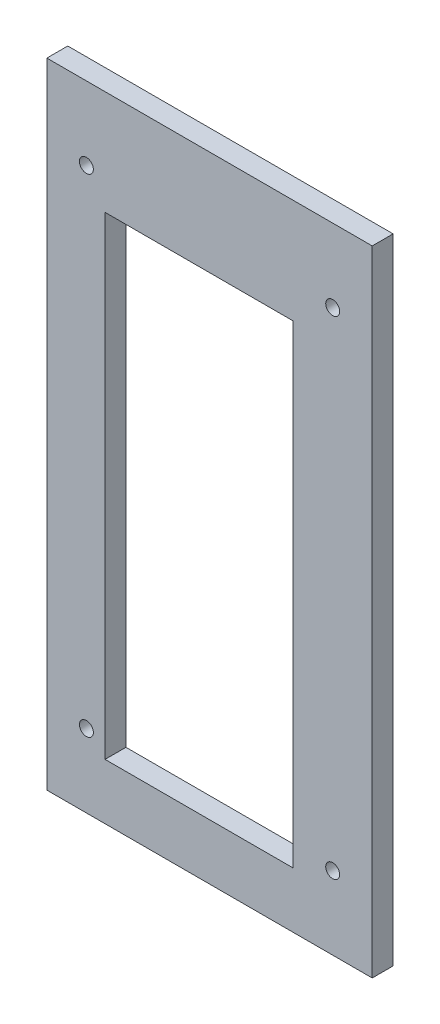
SolidWorks part; units mm, degrees
ref_plane "Front Plane" through (0, 0, 0) normal (0, 0, 1) x (1, 0, 0)
ref_plane "Top Plane" through (0, 0, 0) normal (0, 1, 0) x (1, 0, 0)
ref_plane "Right Plane" through (0, 0, 0) normal (1, 0, 0) x (0, 0, -1)
sketch "Sketch1" plane through (0, 0, 0) normal (0, 0, 1) x (1, 0, 0)
  line L0 (-17.675, 45.5) -> (-17.675, -45.5) construction
  line L1 (-23.35, 45.5) -> (23.35, 45.5)
  line L2 (-23.35, 45.5) -> (-23.35, -45.5)
  line L3 (-23.35, -45.5) -> (23.35, -45.5)
  line L4 (23.35, 45.5) -> (23.35, -45.5)
  line L5 (-23.35, 45.5) -> (23.35, -45.5) construction
  line L6 (-23.35, -45.5) -> (23.35, 45.5) construction
  line L7 (17.675, 45.5) -> (17.675, -45.5) construction
  line L8 (-15, 45.5) -> (-15, -45.5) construction
  line L9 (-15, 30.5) -> (12, 30.5)
  line L10 (-15, 30.5) -> (-15, -37.5)
  line L11 (-15, -37.5) -> (12, -37.5)
  line L12 (12, 30.5) -> (12, -37.5)
  line L13 (-20.35, -45.5) -> (-20.35, 45.5) construction
  line L14 (15, 45.5) -> (15, -45.5) construction
  line L15 (20.35, -45.5) -> (20.35, 45.5) construction
  line L16 (-21, 11.5) -> (21, 11.5) construction
  line L17 (-23.35, 0) -> (23.35, 0) construction
  line L18 (0, 45.5) -> (0, -45.5) construction
  circle A0 centre (17.675, 35) radius 1
  circle A1 centre (17.675, -35) radius 1
  circle A2 centre (-17.675, 35) radius 1
  circle A3 centre (-17.675, -35) radius 1
  point P0 (0, 0)
  dimension "D7" = 2
  dimension "D8" = 70
  dimension "D9" = 70
  dimension "D14" = 35
  dimension "D2" = 27
  dimension "D3" = 3
  dimension "D4" = 3
  dimension "D5" = 46.7
  dimension "D6" = 3
  dimension "D10" = 5.35
  dimension "D11" = 2.675
  dimension "D12" = 0
  dimension "5.65" = 5.35
  dimension "D13" = 2.675
  dimension "D15" = 19
  dimension "D16" = 49
  dimension "D17" = 15
  dimension "D18" = 10.5
  dimension "D20" = 91
extrude "Boss-Extrude1" add sketch "Sketch1" along normal blind 3
